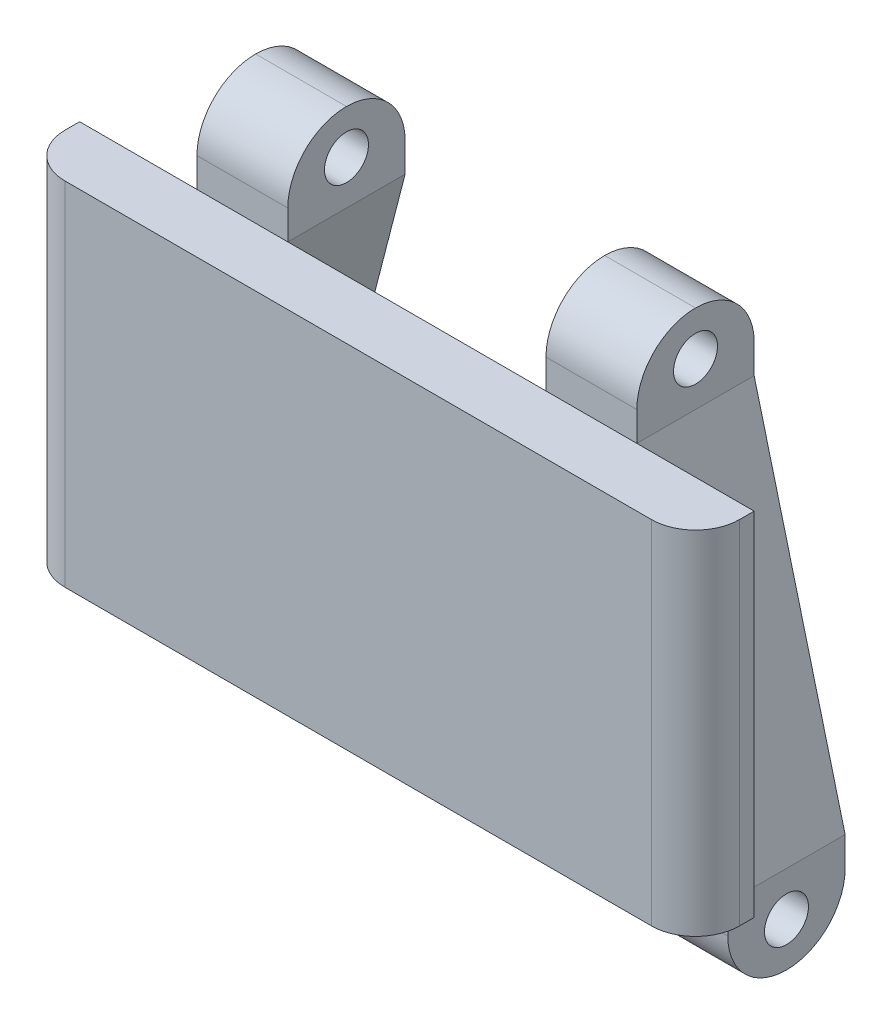
SolidWorks part; units mm, degrees
ref_plane "Front Plane" through (0, 0, 0) normal (0, 0, 1) x (1, 0, 0)
ref_plane "Top Plane" through (0, 0, 0) normal (0, 1, 0) x (1, 0, 0)
ref_plane "Right Plane" through (0, 0, 0) normal (1, 0, 0) x (0, 0, -1)
sketch "Sketch2" plane through (0, 0, 0) normal (0, 0, 1) x (1, 0, 0)
  line L1 (-11.5, -6) -> (11.5, -6)
  line L2 (-11.5, -6) -> (-11.5, 6)
  line L3 (-11.5, 6) -> (11.5, 6)
  line L4 (11.5, -6) -> (11.5, 6)
  line L5 (-11.5, -6) -> (11.5, 6) construction
  line L6 (-11.5, 6) -> (11.5, -6) construction
  point P0 (0, 0)
  dimension "D1" = 23
  dimension "D2" = 12
extrude "Boss-Extrude2" add sketch "Sketch2" along normal blind 2
fillet "Fillet3" radius 1.5 2 edges at (-11.5, 0, 2) (11.5, 0, 2)
sketch "Sketch3" plane through (0, 0, 0) normal (0, 0, -1) x (-1, 0, 0)
  line L0 (-10.6026, -6) -> (-7.5, 6)
  line L1 (11.5, -6) -> (-11.5, -6) construction
  line L2 (-11.5, 6) -> (11.5, 6) construction
  line L3 (-7.504, -6) -> (-4.4013, 6)
  line L4 (0, 6) -> (0, -11.5661) construction
  line L6 (-7.5, 6) -> (-4.4013, 6)
  line L10 (-10.6026, -6) -> (-7.504, -6)
  line L15 (7.504, -6) -> (4.4013, 6)
  line L16 (10.6026, -6) -> (7.5, 6)
  line L20 (-7.5, 6) -> (-4.4013, 6)
  line L21 (-7.5, 6) -> (-7.5, 9)
  line L22 (-7.5, 9) -> (-4.4013, 9)
  line L23 (-4.4013, 6) -> (-4.4013, 9)
  line L24 (-10.6026, -6) -> (-7.504, -6)
  line L25 (-10.6026, -6) -> (-10.6026, -9)
  line L26 (-10.6026, -9) -> (-7.504, -9)
  line L27 (-7.504, -6) -> (-7.504, -9)
  line L31 (7.504, -6) -> (7.504, -9)
  line L32 (10.6026, -9) -> (7.504, -9)
  line L33 (10.6026, -6) -> (10.6026, -9)
  line L34 (7.5, 9) -> (4.4013, 9)
  line L35 (4.4013, 6) -> (4.4013, 9)
  line L36 (7.5, 6) -> (7.5, 9)
  line L37 (-7.5, 6) -> (-7.504, -8.5888) construction
  line L38 (7.5, 6) -> (7.504, -6) construction
  dimension "D1" = 3
  dimension "D2" = 3
  dimension "D3" = 3
  dimension "D4" = 4
extrude "Boss-Extrude4" add sketch "Sketch3" along normal blind 4
fillet "Fillet4" radius 2 8 edges at (-9.0533, -9, 0) (-9.0533, -9, -4) (9.0533, -9, 0) (9.0533, -9, -4) (5.9507, 9, 0) (5.9507, 9, -4) (-5.9507, 9, 0) (-5.9507, 9, -4)
sketch "Sketch5" plane through (7.5, 0, 0) normal (1, 0, 0) x (0, 0, -1)
  line L0 (0, 0) -> (14.0447, 0) construction
  line L1 (4, 6) -> (0, 6) construction
  line L2 (2, 6) -> (2, 11.3819) construction
  line L3 (2, 9) -> (10.2486, 9) construction
  line L4 (10.2486, 9) -> (-5.8127, 9) construction
  line L5 (2, 6) -> (11.6825, 6) construction
  line L6 (4, 6) -> (4, 10.1274) construction
  circle A1 centre (2, 7.5) radius 0.75
  circle A2 centre (2, -7.5) radius 0.75
  dimension "D1" = 1.5
  dimension "D2" = 1.5
hole_wizard "Ø1.5mm Dowel Hole1" positions "3DSketch2" profile "Sketch9" hole size "Ø1.5" standard "BSI"
sketch3d "3DSketch2"
  point P0 (7.5, 7.5, -2)
  point P3 (7.5, -7.5, -2)
sketch "Sketch9" plane through (7.5, 7.5, -2) normal (0, 1, 0) x (0, 0, -1)
  line L0 (0, 0) -> (0, 30000)
  line L1 (0, 30000) -> (0.75, 29999.5494)
  line L2 (0.75, 29999.5494) -> (0.75, 0)
  line L5 (0.75, 0) -> (0, 0)
  line L10 (0, 30000) -> (-0.75, 29999.5494) construction
  line L11 (0, -6.35) -> (0, 107.95) construction
  dimension "Hole Dia." = 1.5
  dimension "Hole Depth" = 30000
  dimension "Drill Angle" = 118
hole_wizard "Ø1.5mm Dowel Hole2" positions "3DSketch3" profile "Sketch10" hole size "Ø1.5" standard "BSI"
sketch3d "3DSketch3"
  point P0 (7.5, -7.5, -2)
sketch "Sketch10" plane through (7.5, -7.5, -2) normal (0, 1, 0) x (0, 0, 1)
  line L0 (0, 0) -> (0, 30000)
  line L1 (0, 30000) -> (0.75, 29999.5494)
  line L2 (0.75, 29999.5494) -> (0.75, 0)
  line L5 (0.75, 0) -> (0, 0)
  line L10 (0, 30000) -> (-0.75, 29999.5494) construction
  line L11 (0, -6.35) -> (0, 107.95) construction
  dimension "Hole Dia." = 1.5
  dimension "Hole Depth" = 30000
  dimension "Drill Angle" = 118
